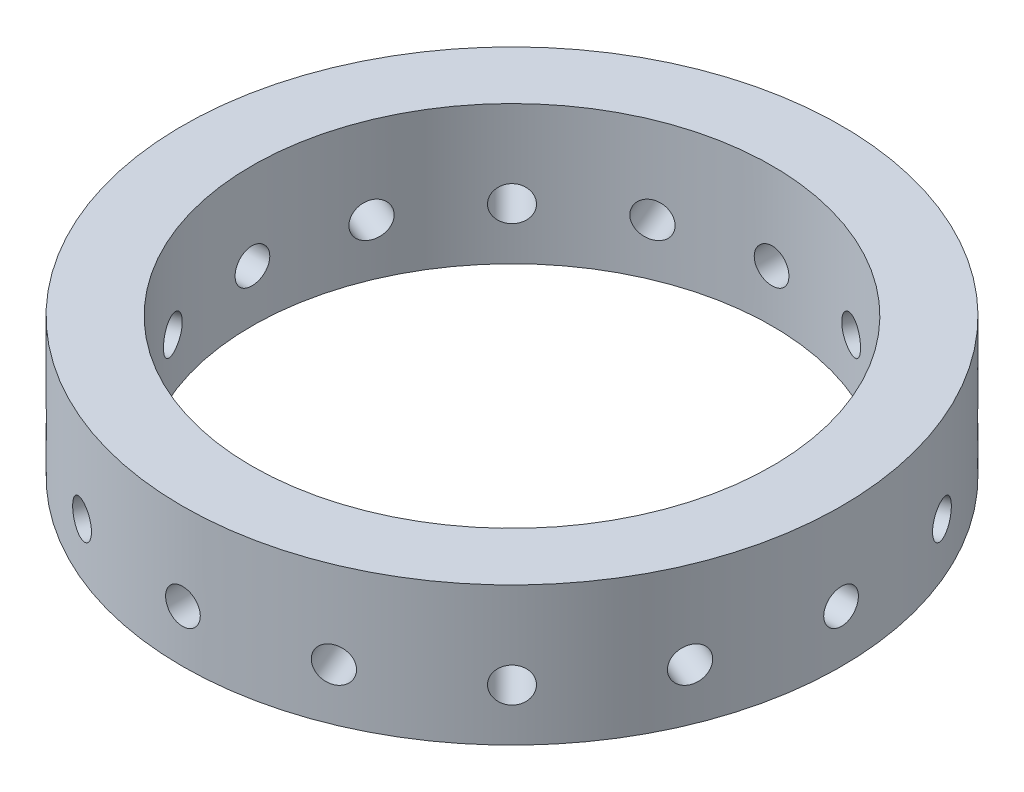
SolidWorks part; units mm, degrees
material "6061-T6 (SS)"
ref_plane "Front Plane" through (0, 0, 0) normal (0, 0, 1) x (1, 0, 0)
ref_plane "Top Plane" through (0, 0, 0) normal (0, 1, 0) x (1, 0, 0)
ref_plane "Right Plane" through (0, 0, 0) normal (1, 0, 0) x (0, 0, -1)
sketch "Sketch1" plane through (0, 0, 0) normal (0, 1, 0) x (1, 0, 0)
  circle A0 centre (0, 0) radius 60.325
  circle A1 centre (0, 0) radius 47.625
extrude "Boss-Extrude1" add sketch "Sketch1" along normal blind 25.4
ref_plane "Plane1" through (0, 0, -60.325) normal (0, 0, -1) x (-1, 0, 0)
sketch "Sketch2" plane through (0, 0, -60.325) normal (0, 0, -1) x (-1, 0, 0)
  line L0 (0, 0) -> (0, 9.525)
  point P4 (0, 9.525)
hole_wizard "1/4 (0.25) Diameter Hole1" positions "Sketch3" profile "Sketch4" hole size "1/4" standard "ANSI Inch" end condition through all
sketch "Sketch3" plane through (0, 0, -60.325) normal (0, 0, -1) x (-1, 0, 0)
  point P0 (0, 9.525)
sketch "Sketch4" plane through (0, 9.525, -60.325) normal (1, 0, 0) x (0, 1, 0)
  line L0 (0, 0) -> (0, 120.65)
  line L1 (0, 120.65) -> (3.175, 120.65)
  line L2 (3.175, 120.65) -> (3.175, 0)
  line L5 (3.175, 0) -> (0, 0)
  line L11 (0, -6.35) -> (0, 107.95) construction
  dimension "Thru Hole Dia." = 6.35
  dimension "Thru Hole Depth" = 120.65
sketch "Sketch5" plane through (0, 0, 0) normal (0, 0, 1) x (1, 0, 0)
  line L0 (0, 0) -> (0, 24.4952)
pattern_circular "CirPattern1" count 16 over 360 about axis through (0, 0, 0) along (0, 1, 0) of "1/4 (0.25) Diameter Hole1" reverse direction yes
ref_plane "Plane2" through (0, 9.525, 0) normal (0, 1, 0) x (1, 0, 0)
